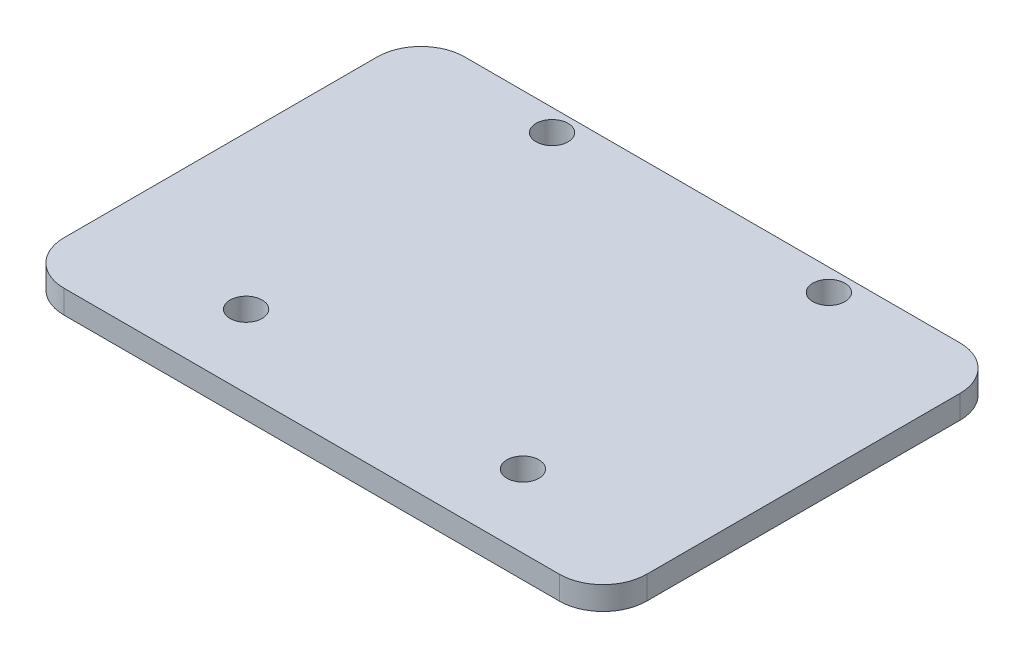
SolidWorks part; units mm, degrees
ref_plane "Front Plane" through (0, 0, 0) normal (0, 0, 1) x (1, 0, 0)
ref_plane "Top Plane" through (0, 0, 0) normal (0, 1, 0) x (1, 0, 0)
ref_plane "Right Plane" through (0, 0, 0) normal (1, 0, 0) x (0, 0, -1)
sketch "Sketch1" plane through (0, 0, 0) normal (0, 1, 0) x (1, 0, 0)
  line L0 (-20, 13.75) -> (20, -13.75) construction
  line L1 (-20, 13.75) -> (20, 13.75)
  line L2 (-20, 13.75) -> (-20, -13.75)
  line L3 (-20, -13.75) -> (20, -13.75)
  line L4 (20, 13.75) -> (20, -13.75)
  dimension "D1" = 40
  dimension "D2" = 27.5
extrude "Boss-Extrude1" add sketch "Sketch1" along normal blind 1.6
hole_wizard "M2 Clearance Hole1" positions "Sketch2" profile "Sketch3" hole size "M2" standard "ANSI Metric"
sketch "Sketch2" plane through (0, 1.6, 0) normal (0, 1, 0) x (1, 0, 0)
  line L1 (-9.5, 12.25) -> (9.5, 12.25)
  line L2 (-9.5, 12.25) -> (-9.5, -8.75)
  line L3 (-9.5, -8.75) -> (9.5, -8.75)
  line L4 (9.5, 12.25) -> (9.5, -8.75)
  line L5 (-20, -13.75) -> (20, -13.75) construction
  point P0 (-9.5, 12.25)
  point P2 (9.5, 12.25)
  point P4 (9.5, -8.75)
  point P6 (-9.5, -8.75)
  point P142 (0, -8.75)
  dimension "D1" = 21
  dimension "D2" = 19
  dimension "D3" = 5
sketch "Sketch3" plane through (-9.5, 1.6, -12.25) normal (1, 0, 0) x (0, 0, 1)
  line L0 (0, 0) -> (0, 5.8609)
  line L1 (0, 5.8609) -> (1.1, 5.2)
  line L2 (1.1, 5.2) -> (1.1, 0)
  line L5 (1.1, 0) -> (0, 0)
  line L10 (0, 5.8609) -> (-1.1, 5.2) construction
  line L11 (0, -6.35) -> (0, 107.95) construction
  dimension "Hole Dia." = 2.2
  dimension "Hole Depth" = 5.2
  dimension "Drill Angle" = 118
fillet "Fillet1" radius 3 4 edges at (20, 0.8, -13.75) (20, 0.8, 13.75) (-20, 0.8, 13.75) (-20, 0.8, -13.75)
